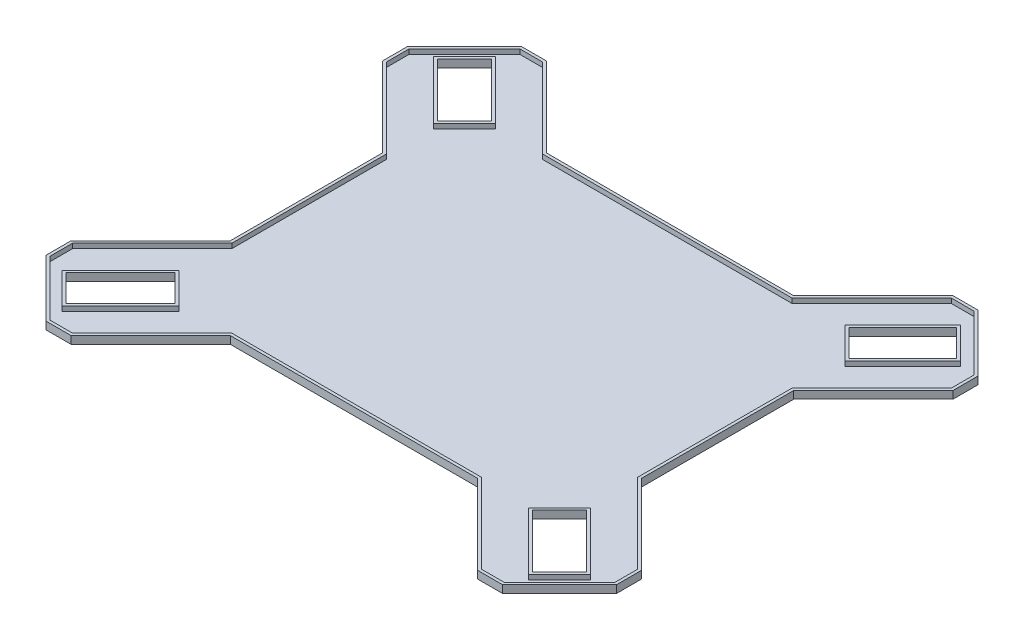
SolidWorks part; units mm, degrees
ref_plane "Front Plane" through (0, 0, 0) normal (0, 0, 1) x (1, 0, 0)
ref_plane "Top Plane" through (0, 0, 0) normal (0, 1, 0) x (1, 0, 0)
ref_plane "Right Plane" through (0, 0, 0) normal (1, 0, 0) x (0, 0, -1)
sketch "Sketch1" plane through (0, 0, 0) normal (0, 1, 0) x (1, 0, 0)
  line L0 (-87.8512, 52.9103) -> (152.1488, 52.9103)
  line L1 (182.1488, 22.9103) -> (182.1488, -167.0897)
  line L2 (152.1488, -197.0897) -> (-87.8512, -197.0897)
  line L3 (-117.8512, -167.0897) -> (-117.8512, 22.9103)
  line L4 (-117.8512, 22.9103) -> (-87.8512, 52.9103)
  line L5 (-87.8512, -197.0897) -> (-117.8512, -167.0897)
  line L6 (182.1488, -167.0897) -> (152.1488, -197.0897)
  line L7 (152.1488, 52.9103) -> (182.1488, 22.9103)
  point P0 (-117.8512, 52.9103)
  point P1 (182.1488, 52.9103)
  point P3 (182.1488, -197.0897)
  point P4 (-117.8512, -197.0897)
  dimension "D1" = 300
  dimension "D2" = 250
extrude "Boss-Extrude1" add sketch "Sketch1" along normal blind 4
sketch "Sketch2" plane through (0, 4, 0) normal (0, 1, 0) x (1, 0, 0)
  line L0 (-87.8512, -197.0897) -> (-117.8512, -167.0897)
  line L1 (-102.8512, -182.0897) -> (-68.9101, -148.1486) construction
  line L2 (-117.8512, 22.9103) -> (-87.8512, 52.9103) construction
  line L3 (-87.8512, 52.9103) -> (-102.8512, 37.9103) construction
  line L4 (-102.8512, 37.9103) -> (-68.9101, 3.9691) construction
  line L5 (152.1488, 52.9103) -> (182.1488, 22.9103) construction
  line L6 (182.1488, 22.9103) -> (167.1488, 37.9103) construction
  line L7 (167.1488, 37.9103) -> (133.2077, 3.9691) construction
  line L8 (152.1488, -197.0897) -> (182.1488, -167.0897) construction
  line L9 (152.1488, -197.0897) -> (182.1488, -167.0897) construction
  line L10 (167.1488, -182.0897) -> (133.2077, -148.1486) construction
  line L11 (-68.9101, -148.1486) -> (-75.9811, -141.0775)
  line L12 (-75.9811, -141.0775) -> (-68.9101, -148.1486)
  line L13 (-68.9101, -148.1486) -> (-61.839, -155.2197)
  line L14 (-75.9811, -141.0775) -> (-104.7025, -169.7989)
  line L15 (-104.7025, -169.7989) -> (-90.5507, -183.9508)
  line L16 (-90.5507, -183.9508) -> (-61.839, -155.2197)
  line L17 (-68.9101, 3.9691) -> (-61.839, 11.0402)
  line L18 (-61.839, 11.0402) -> (-68.9101, 3.9691)
  line L19 (-68.9101, 3.9691) -> (-75.9811, -3.1019)
  line L20 (-75.9811, -3.1019) -> (-104.2654, 25.1823)
  line L21 (-61.839, 11.0402) -> (-90.1233, 39.3245)
  line L22 (-90.1233, 39.3245) -> (-104.2654, 25.1823)
  line L23 (167.1488, 37.9103) -> (174.2199, 30.8392) construction
  line L24 (167.1488, 37.9103) -> (160.0777, 44.9813) construction
  line L25 (174.2199, 30.8392) -> (168.563, 25.1823) construction
  line L26 (160.0777, 44.9813) -> (154.4209, 39.3245) construction
  line L27 (154.4209, 39.3245) -> (168.563, 25.1823)
  line L28 (133.2077, -148.1486) -> (126.1366, -155.2197)
  line L29 (133.2077, -148.1486) -> (140.2787, -141.0775)
  line L30 (126.1366, -155.2197) -> (154.4209, -183.504)
  line L31 (140.2787, -141.0775) -> (168.563, -169.3618)
  line L32 (168.563, -169.3618) -> (154.4209, -183.504)
  line L33 (156.7347, -181.1901) -> (162.3916, -186.847) construction
  line L34 (168.563, 25.1823) -> (140.2787, -3.1019)
  line L35 (140.2787, -3.1019) -> (133.2077, 3.9691)
  line L36 (133.2077, 3.9691) -> (126.1366, 11.0402)
  line L37 (126.1366, 11.0402) -> (154.4209, 39.3245)
  line L38 (-117.8512, -72.0897) -> (-75.9811, -72.0897)
  line L39 (-117.8512, 22.9103) -> (-117.8512, -167.0897) construction
  line L40 (182.1488, -72.0897) -> (140.2787, -72.0897)
  line L41 (182.1488, -167.0897) -> (182.1488, 22.9103) construction
  line L42 (-75.9811, -72.0897) -> (-75.9811, -32.0897)
  line L43 (-75.9811, -72.0897) -> (-75.9811, -112.0897)
  line L44 (140.2787, -72.0897) -> (140.2787, -112.0897)
  line L45 (140.2787, -72.0897) -> (140.2787, -32.0897)
  line L46 (-75.9811, -112.0897) -> (-117.8512, -153.9598)
  line L47 (-75.9811, -32.0897) -> (-117.8512, 9.7803)
  line L48 (-117.8512, 9.7803) -> (-117.8512, -153.9598)
  line L49 (140.2787, -32.0897) -> (182.1488, 9.7803)
  line L50 (140.2787, -112.0897) -> (182.1488, -153.9598)
  line L51 (182.1488, -153.9598) -> (182.1488, 9.7803)
  line L52 (-87.8512, 52.9103) -> (-74.7212, 52.9103)
  line L53 (152.1488, 52.9103) -> (-87.8512, 52.9103) construction
  line L54 (32.1488, 52.9103) -> (32.1488, 11.0402)
  line L55 (-74.7212, 52.9103) -> (-32.8511, 11.0402)
  line L56 (-32.8511, 11.0402) -> (32.1488, 11.0402)
  line L57 (32.1488, 52.9103) -> (139.0188, 52.9103)
  line L58 (32.1488, 52.9103) -> (-74.7212, 52.9103)
  line L59 (-74.7212, 52.9103) -> (-75.0161, 53.6429)
  line L60 (139.0188, 52.9103) -> (97.1489, 11.0402)
  line L61 (97.1489, 11.0402) -> (32.1488, 11.0402)
  line L62 (32.1488, -197.0897) -> (32.1488, -155.2197)
  line L63 (-87.8512, -197.0897) -> (152.1488, -197.0897) construction
  line L64 (32.1488, -155.2197) -> (-32.8511, -155.2197)
  line L65 (32.1488, -155.2197) -> (97.1489, -155.2197)
  line L66 (152.1488, -197.0897) -> (139.0188, -197.0897)
  line L67 (139.0188, -197.0897) -> (97.1489, -155.2197)
  line L68 (-87.8512, -197.0897) -> (-74.7212, -197.0897)
  line L69 (-74.7212, -197.0897) -> (-32.8511, -155.2197)
  line L70 (-74.7212, -197.0897) -> (139.0188, -197.0897)
  line M4 (-87.8512, -197.0897) -> (152.1488, -197.0897)
  line M8 (152.1488, 52.9103) -> (-87.8512, 52.9103)
  dimension "D1" = 48
  dimension "D2" = 48
  dimension "D3" = 10
  dimension "D4" = 48
  dimension "D5" = 10
  dimension "D6" = 10
  dimension "D7" = 40
  dimension "D8" = 20
  dimension "D9" = 10
  dimension "D10" = 10
  dimension "D11" = 10
  dimension "D12" = 8
  dimension "D13" = 8
  dimension "D14" = 10
  dimension "D15" = 10
  dimension "D16" = 10
  dimension "D17" = 10
  dimension "D18" = 40
  dimension "D19" = 40
  dimension "D20" = 20
  dimension "D21" = 40
  dimension "D22" = 40
  dimension "D23" = 41.8701
  dimension "D24" = 41.8701
  dimension "D25" = 40
  dimension "D26" = 40
  dimension "D27" = 40
  dimension "D28" = 40
  dimension "D29" = 13.1299
  dimension "D30" = 13.13
  dimension "D31" = 106.87
  dimension "D32" = 130
  dimension "D33" = 13.13
  dimension "D34" = 13.13
extrude "Cut-Extrude1" cut sketch "Sketch2" against normal blind 5 contours L43 L46 L48 L47 L42
extrude "Cut-Extrude3" cut sketch "Sketch2<5>" against normal blind 5 contours L44 L50 L51 L49 L45
sketch "Sketch2<5>" plane through (0, 4, 0) normal (0, 1, 0) x (1, 0, 0) same geometry as "Sketch2"
extrude "Cut-Extrude4" cut sketch "Sketch2<6>" against normal blind 5 contours L21 L22 L20 L19 L17 | L37 L36 L35 L34 L27 | L32 L31 L29 L28 L30 | L15 L16 L13 L11 L14 region at (-83.27, 4, 162.5134) region at (-83.0522, 4, -18.1113) region at (147.3498, 4, -18.1113) region at (147.3498, 4, 162.2907)
sketch "Sketch2<6>" plane through (0, 4, 0) normal (0, 1, 0) x (1, 0, 0) same geometry as "Sketch2"
extrude "Cut-Extrude5" cut sketch "Sketch2<7>" against normal blind 5 contours L61 L60 L54 M8 | L55 L56 L54 M8 | L69 L62 L64 M4 | L67 L65 L62 M4 region at (75.9663, 4, -33.6753) region at (-11.6687, 4, -33.6753) region at (-11.6687, 4, 177.8547) region at (75.9663, 4, 177.8547)
sketch "Sketch2<7>" plane through (0, 4, 0) normal (0, 1, 0) x (1, 0, 0) same geometry as "Sketch2"
shell "Shell1" thickness 1.5 removed face at (147.3498, 4, 162.2907)
